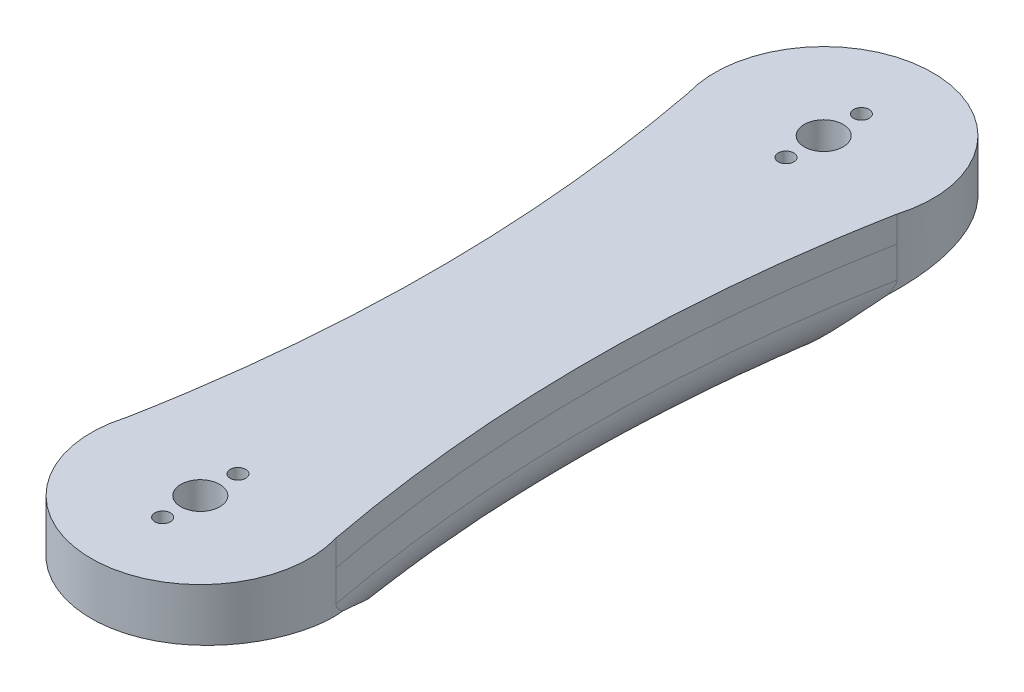
SolidWorks part; units mm, degrees
ref_plane "Front Plane" through (0, 0, 0) normal (0, 0, 1) x (1, 0, 0)
ref_plane "Top Plane" through (0, 0, 0) normal (0, 1, 0) x (1, 0, 0)
ref_plane "Right Plane" through (0, 0, 0) normal (1, 0, 0) x (0, 0, -1)
sketch "Sketch1" plane through (0, 0, 0) normal (0, 1, 0) x (1, 0, 0)
  line L0 (0, 120) -> (0, 0) construction
  line L1 (-20.1246, 6) -> (20.1246, 6) construction
  line L2 (-20.1246, 114) -> (20.1246, 114) construction
  circle A0 centre (0, 0) radius 21
  circle A1 centre (0, 120) radius 21
  spline S0 degree 2 poles (-20.1246, 114) (-9.8754, 60) (-20.1246, 6) knots 0 0 0 1 1 1
  spline S1 degree 2 poles (20.1246, 114) (9.8754, 60) (20.1246, 6) knots 0 0 0 1 1 1
  point P10 (0, 60)
  dimension "D1" = 42
  dimension "D2" = 120
  dimension "D3" = 6
  dimension "D4" = 6
  dimension "D5" = 60
  dimension "D6" = 15
extrude "Boss-Extrude1" add sketch "Sketch1" along normal blind 16 contours S1 A1 S0 A0 region at (0, 0, -60)
extrude "Boss-Extrude2" add sketch "Sketch1<3>" along normal blind 21 contours A0 | A1
sketch "Sketch1<3>" plane through (0, 0, 0) normal (0, 1, 0) x (1, 0, 0) same geometry as "Sketch1"
sketch "Sketch2" plane through (0, 0, 0) normal (1, 0, 0) x (0, 0, -1)
  line L0 (-21, 11) -> (-21, 0)
  line L1 (-21, 21) -> (-21, 0) construction
  line L2 (-21, 0) -> (21, 0)
  line L3 (141, 0) -> (141, 11)
  line L4 (141, 0) -> (141, 21) construction
  line L5 (99, 0) -> (141, 0)
  spline S0 degree 2 poles (-21, 11) (10.7985, 10.9443) (21, 0) knots 0 0 0 1 1 1
  spline S1 degree 2 poles (141, 11) (111.286, 12.2125) (99, 0) knots 0 0 0 1 1 1
  dimension "D1" = 11
  dimension "D2" = 42
  dimension "D3" = 42
  dimension "D4" = 11
extrude "Cut-Extrude3" cut sketch "Sketch2" against normal through all both and the other way through all
ref_plane "Plane1" through (0, 15, 0) normal (0, 1, 0) x (1, 0, 0)
fillet "Fillet1" radius 10 2 edges
sketch "Sketch4" plane through (0, 15, 0) normal (0, 1, 0) x (1, 0, 0)
  arc A2 (-20.1246, 114) -> (20.1246, 114) centre (0, 120) ccw
  arc A3 (20.1246, 6) -> (-20.1246, 6) centre (0, 0) ccw
  arc A4 (-20.1246, 114) -> (20.1246, 114) centre (0, 120) ccw
  arc A5 (20.1246, 6) -> (-20.1246, 6) centre (0, 0) ccw
  parabola Q2 (20.1246, 6) -> (20.1246, 114) focus (157.2547, 60) apex (15, 60)
  parabola Q3 (-20.1246, 114) -> (-20.1246, 6) focus (-157.2547, 60) apex (-15, 60)
  parabola Q4 (20.1246, 6) -> (20.1246, 114) focus (157.2547, 60) apex (15, 60)
  parabola Q5 (-20.1246, 114) -> (-20.1246, 6) focus (-157.2547, 60) apex (-15, 60)
  dimension "D1" = 0
extrude "Boss-Extrude3" add sketch "Sketch4" along normal up to surface (6 mm away) up to face at (0, 21, 21)
sketch "Sketch5" plane through (0, 0, 0) normal (0, 0, 1) x (1, 0, 0)
  circle A0 centre (0, 9) radius 5.75
  dimension "D1" = 11.5
  dimension "D2" = 9
extrude "Cut-Extrude4" cut sketch "Sketch5" against normal blind 124
sketch "Sketch6" plane through (0, 15, 0) normal (0, 1, 0) x (1, 0, 0)
  arc A2 (17.2497, 114.8571) -> (-17.2497, 114.8571) centre (0, 120) ccw
  circle A3 centre (0, 120) radius 18
  arc A5 (-17.2497, 5.1429) -> (17.2497, 5.1429) centre (0, 0) ccw
  circle A6 centre (0, 0) radius 18
  dimension "D1" = 3
  dimension "D2" = 3
extrude "Cut-Extrude5" cut sketch "Sketch6" against normal blind 33
sketch "Sketch7" plane through (0, 15, 0) normal (0, -1, 0) x (1, 0, 0)
  line L0 (0, 7.25) -> (0, -7.25) construction
  line L1 (0, 0) -> (0, -120) construction
  line L2 (0, -60) -> (-50.1503, -60) construction
  circle A0 centre (0, 0) radius 3.75
  circle A1 centre (0, 7.25) radius 1.5
  circle A2 centre (0, -7.25) radius 1.5
  circle A3 centre (0, -112.75) radius 1.5
  circle A4 centre (0, -120) radius 3.75
  circle A5 centre (0, -127.25) radius 1.5
  dimension "D1" = 7.5
  dimension "D2" = 3
  dimension "D3" = 3
  dimension "D4" = 7.25
extrude "Cut-Extrude6" cut sketch "Sketch7" against normal through all
sketch "Sketch8" plane through (0, 21, 0) normal (0, 1, 0) x (1, 0, 0)
  point P0 (0, 0)
  point P1 (0, 120)
